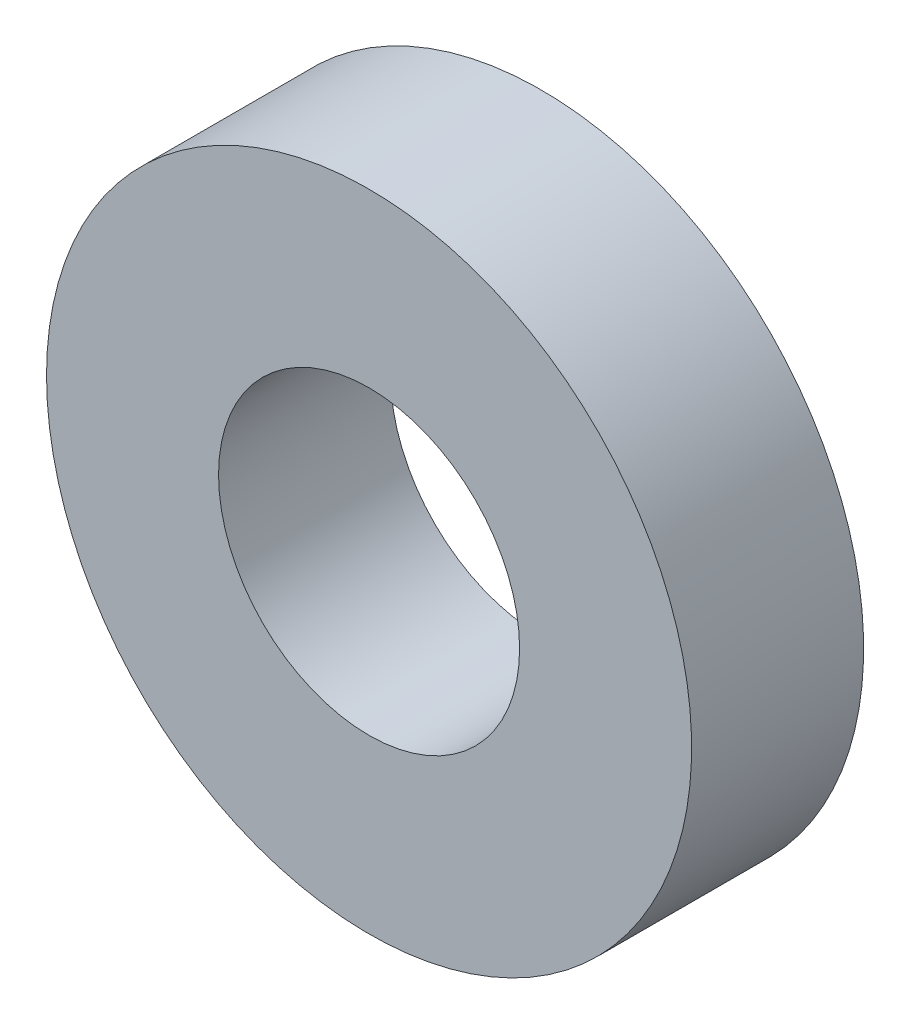
SolidWorks part; units mm, degrees
ref_plane "Спереди" through (0, 0, 0) normal (0, 0, 1) x (1, 0, 0)
ref_plane "Сверху" through (0, 0, 0) normal (0, 1, 0) x (1, 0, 0)
ref_plane "Справа" through (0, 0, 0) normal (1, 0, 0) x (0, 0, -1)
sketch "Эскиз1" plane through (0, 0, 0) normal (0, 0, 1) x (1, 0, 0)
  circle A0 centre (0, 5.8) radius 5.25 construction
  circle A1 centre (0, 5.8) radius 5.25
  circle A2 centre (0, 5.8) radius 11.25
  circle A3 centre (-8.6, -7.0953) radius 2.25 construction
  dimension "D1" = 2
extrude "Бобышка-Вытянуть1" add sketch "Эскиз1" along normal up to surface (6 mm away)
